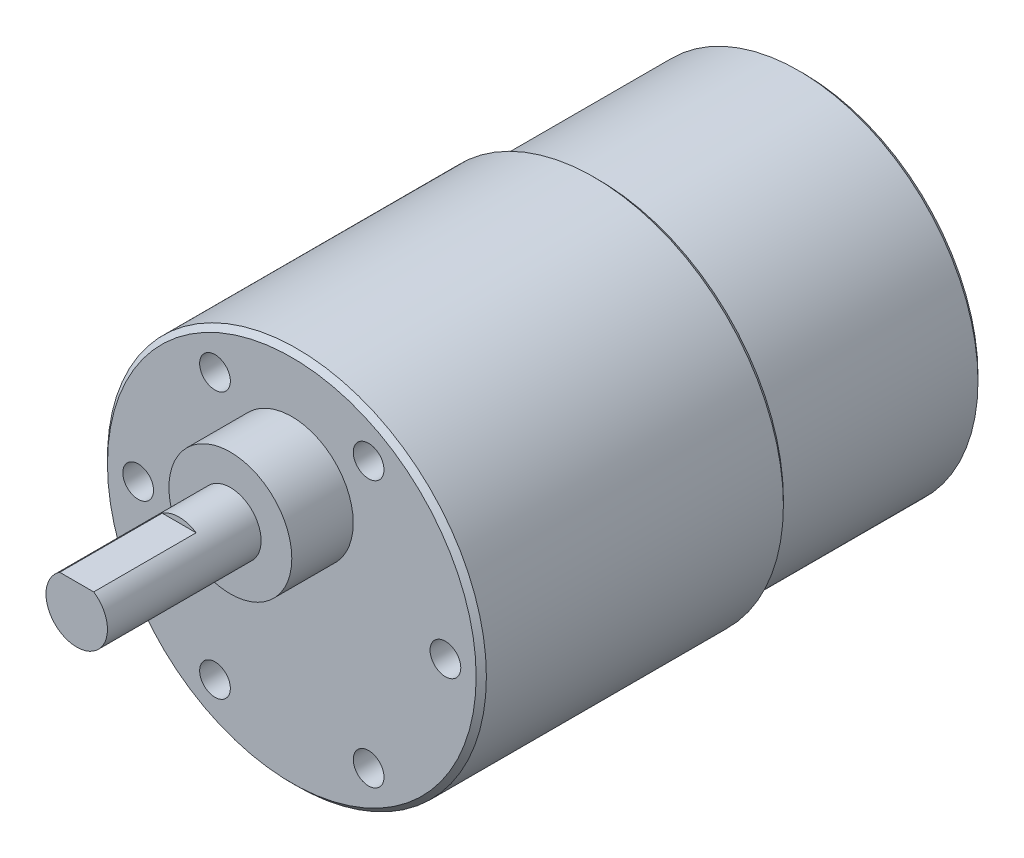
SolidWorks part; units mm, degrees
material "锻制不锈钢"
ref_plane "前视基准面" through (0, 0, 0) normal (0, 0, 1) x (1, 0, 0)
ref_plane "上视基准面" through (0, 0, 0) normal (0, 1, 0) x (1, 0, 0)
ref_plane "右视基准面" through (0, 0, 0) normal (1, 0, 0) x (0, 0, -1)
sketch "草图1" plane through (0, 0, 0) normal (0, 0, 1) x (1, 0, 0)
  line L0 (0, -1000) -> (0, 49000) construction
  circle A0 centre (0, 0) radius 18.5
  circle A1 centre (0, 7) radius 3
  circle A2 centre (0, 0) radius 17.5
  dimension "D1" = 37
  dimension "D2" = 6
  dimension "D3" = 7
  dimension "D4" = 35
extrude "凸台-拉伸1" add sketch "草图1" against normal blind 50 contours A0
sketch "草图2" plane through (0, 0, -50) normal (0, 0, -1) x (-1, 0, 0)
  circle A0 centre (0, 0) radius 5
  dimension "D1" = 10
extrude "凸台-拉伸2" add sketch "草图2" along normal blind 6
extrude "凸台-拉伸3" add sketch "草图1<3>" along normal blind 21 contours A1 L0 | L0 A1 region at (-1.2732, 7, 0) region at (1.2732, 7, 0)
sketch "草图1<3>" plane through (0, 0, 0) normal (0, 0, 1) x (1, 0, 0) same geometry as "草图1"
sketch "草图4" plane through (0, 0, 21) normal (0, 0, 1) x (1, 0, 0)
  line L0 (-1.6583, 9.5) -> (1.6583, 9.5)
  circle A0 centre (0, 7) radius 3
  circle M3 centre (0, 7) radius 3
  dimension "D2" = 6
  dimension "D1" = 2.5
extrude "切除-拉伸1" cut sketch "草图4" against normal blind 10 contours L0 M3 region at (0, 9.7015, 21)
sketch "草图5" plane through (0, 0, 0) normal (0, 0, 1) x (1, 0, 0)
  circle A0 centre (0, 7) radius 6
  dimension "D1" = 12
extrude "凸台-拉伸4" add sketch "草图5" along normal blind 6
extrude "切除-拉伸2" cut sketch "草图1<5>" along normal blind 20 from surface contours L0 A0 A2 | A0 L0 A2 region at (-18.0863, 0, 0) region at (0.4137, -18, 0) starting at face at (-5, 0, -50)
sketch "草图1<5>" plane through (0, 0, 0) normal (0, 0, 1) x (1, 0, 0) same geometry as "草图1"
chamfer "倒角1" distance 0.5 angle 45 4 edges at (-5, 0, -56) (17.5, 0, -50) (18.5, 0, -30) (18.5, 0, 0)
sketch "草图8" plane through (0, 0, 0) normal (0, 0, 1) x (1, 0, 0)
  line L0 (-1000, 0) -> (49000, 0) construction
  circle A0 centre (15, 0) radius 1.5
  circle A1 centre (7.5, -12.9904) radius 1.5
  circle A2 centre (-7.5, -12.9904) radius 1.5
  circle A3 centre (-15, 0) radius 1.5
  circle A4 centre (-7.5, 12.9904) radius 1.5
  circle A5 centre (7.5, 12.9904) radius 1.5
  point P5 (-28.7084, 7.7197)
  point P6 (0, 0)
  point P17 (0, 0)
  dimension "D1" = 3
  dimension "D2" = 15
  dimension "D3" = 6
extrude "切除-拉伸3" cut sketch "草图8" against normal blind 10
